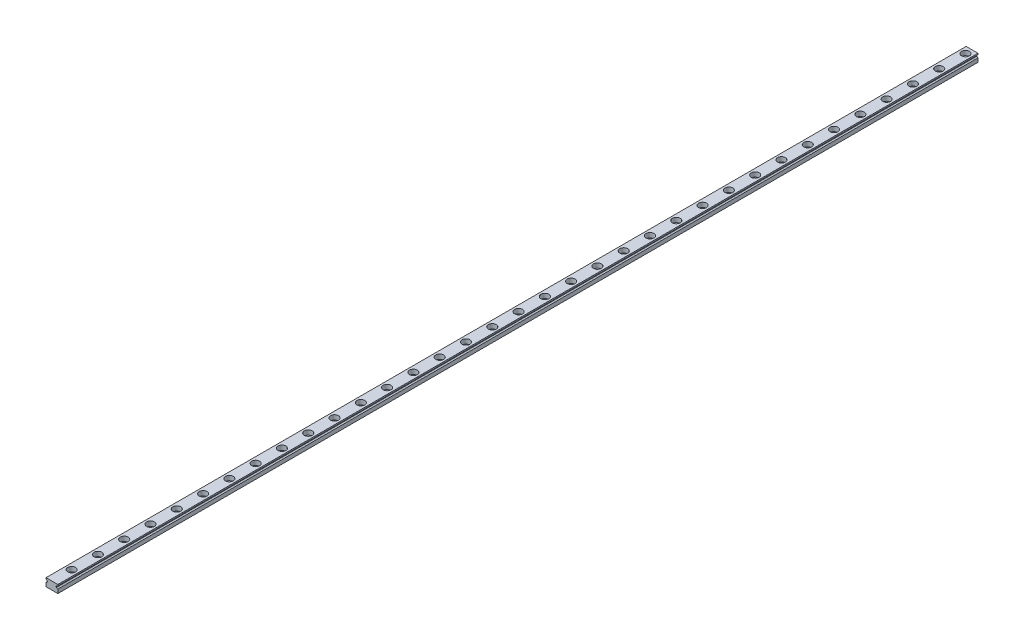
SolidWorks part; units mm, degrees
ref_plane "Front Plane" through (0, 0, 0) normal (0, 0, 1) x (1, 0, 0)
ref_plane "Top Plane" through (0, 0, 0) normal (0, 1, 0) x (1, 0, 0)
ref_plane "Right Plane" through (0, 0, 0) normal (1, 0, 0) x (0, 0, -1)
sketch "Sketch1" plane through (0, 0, 0) normal (0, 0, 1) x (1, 0, 0)
  line L0 (0, 0) -> (0, 5.7299) construction
  line L1 (-4.5, -3) -> (4.5, -3)
  line L2 (-4.5, -3) -> (-4.5, 0)
  line L3 (-4.5, 3) -> (4.5, 3)
  line L4 (4.5, -3) -> (4.5, 0)
  line L5 (-4.5, -3) -> (4.5, 3) construction
  line L6 (-4.5, 3) -> (4.5, -3) construction
  line L7 (-4.5, 2) -> (-4.5, 3)
  line L8 (-3.564, 0.648) -> (-3.2351, 0.648)
  line L9 (3.564, 0.648) -> (3.2351, 0.648)
  line L10 (-3.564, 1.352) -> (-3.2351, 1.352)
  line L11 (-3.2351, 0.648) -> (-3.2351, 1.352)
  line L12 (3.2351, 0.648) -> (3.2351, 1.352)
  line L13 (3.564, 1.352) -> (3.2351, 1.352)
  line L14 (4.5, 2) -> (4.5, 3)
  arc A0 (-3.564, 1.352) -> (-4.5, 2) centre (-4.5, 1) ccw
  arc A1 (-4.5, 0) -> (-3.564, 0.648) centre (-4.5, 1) ccw
  arc A2 (4.5, 0) -> (3.564, 0.648) centre (4.5, 1) cw
  arc A3 (3.564, 1.352) -> (4.5, 2) centre (4.5, 1) cw
  point P0 (0, 0)
  dimension "D3" = 1
  dimension "D1" = 9
  dimension "D2" = 6
  dimension "D4" = 2
extrude "Extrude1" add sketch "Sketch1" along normal blind 700
sketch "Sketch2" plane through (0, 3, 0) normal (0, 1, 0) x (1, 0, 0)
  line L0 (4.5, 0) -> (-4.5, 0) construction
  circle A0 centre (0, -5) radius 1.75
  circle A1 centre (0, -5) radius 3
  dimension "D1" = 3.5
  dimension "D2" = 6
  dimension "D3" = 5
extrude "Extrude2" cut sketch "Sketch2" against normal blind 3.5 contours A1
extrude "Extrude3" cut sketch "Sketch" against normal through all contours A0
sketch "Sketch" plane through (0, 3, 0) normal (0, 1, 0) x (1, 0, 0) same geometry as "Sketch2"
pattern_linear "LPattern1" count 45 spacing 20 along (0, 0, 1) of "Extrude2", "Extrude3"
